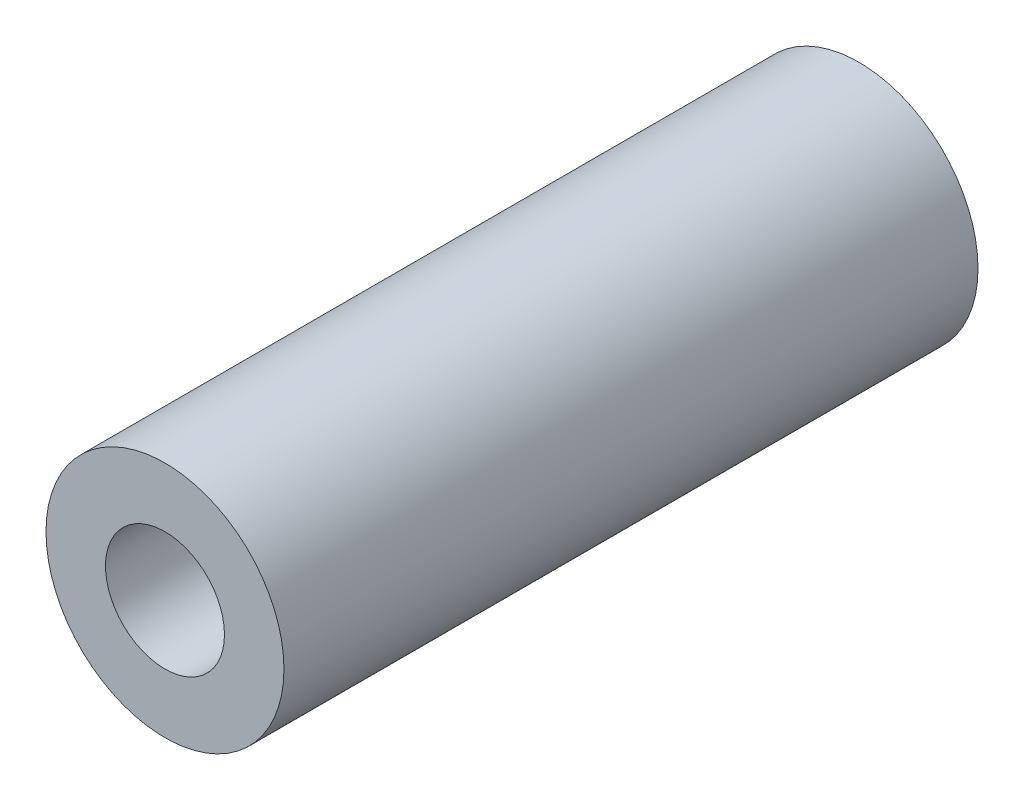
SolidWorks part; units mm, degrees
ref_plane "Alzado" through (0, 0, 0) normal (0, 0, 1) x (1, 0, 0)
ref_plane "Planta" through (0, 0, 0) normal (0, 1, 0) x (1, 0, 0)
ref_plane "Vista lateral" through (0, 0, 0) normal (1, 0, 0) x (0, 0, -1)
sketch "Croquis1" plane through (0, 0, 0) normal (0, 0, 1) x (1, 0, 0)
  circle A0 centre (0, 0) radius 6
  circle A1 centre (0, 0) radius 3
  circle A2 centre (0, 0) radius 1.5
extrude "Saliente-Extruir3" add sketch "Croquis1" along normal blind 35 contours A0 A1 region at (-5.8303, 0, 0)
extrude "Saliente-Extruir4" add sketch "Croquis1<4>" along normal blind 5 contours A1 A2 region at (-2.9151, 0, 0)
sketch "Croquis1<4>" plane through (0, 0, 0) normal (0, 0, 1) x (1, 0, 0) same geometry as "Croquis1"
